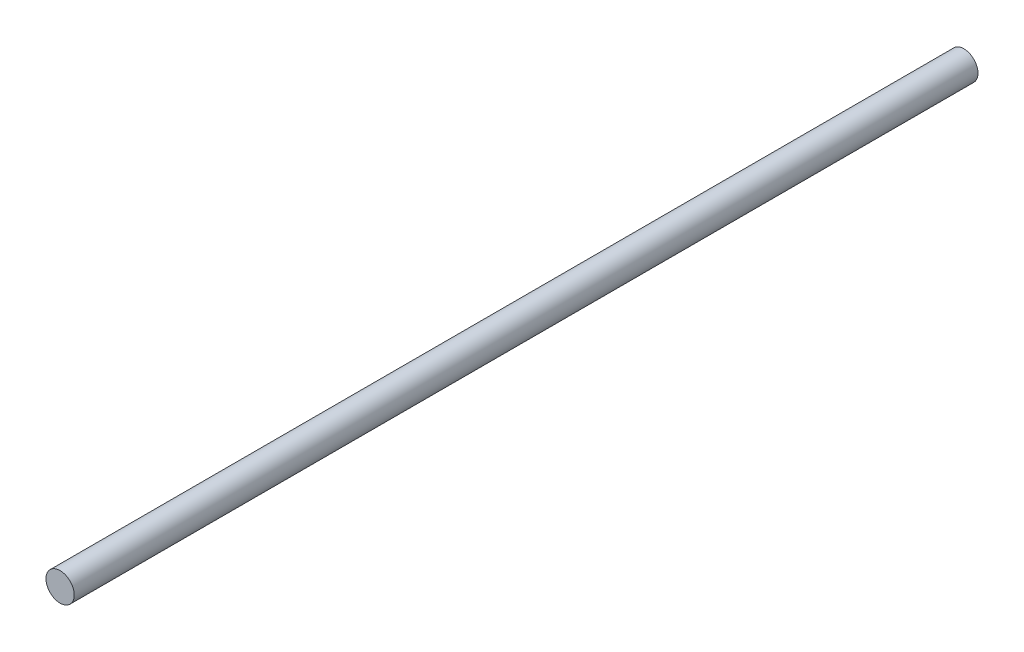
SolidWorks part; units mm, degrees
ref_plane "Front Plane" through (0, 0, 0) normal (0, 0, 1) x (1, 0, 0)
ref_plane "Top Plane" through (0, 0, 0) normal (0, 1, 0) x (1, 0, 0)
ref_plane "Right Plane" through (0, 0, 0) normal (1, 0, 0) x (0, 0, -1)
sketch "Sketch1" plane through (0, 0, 0) normal (0, 0, 1) x (1, 0, 0)
  circle A0 centre (0, 0) radius 6.35
  dimension "D1" = 12.7
extrude "Boss-Extrude1" add sketch "Sketch1" along normal blind 406.4
